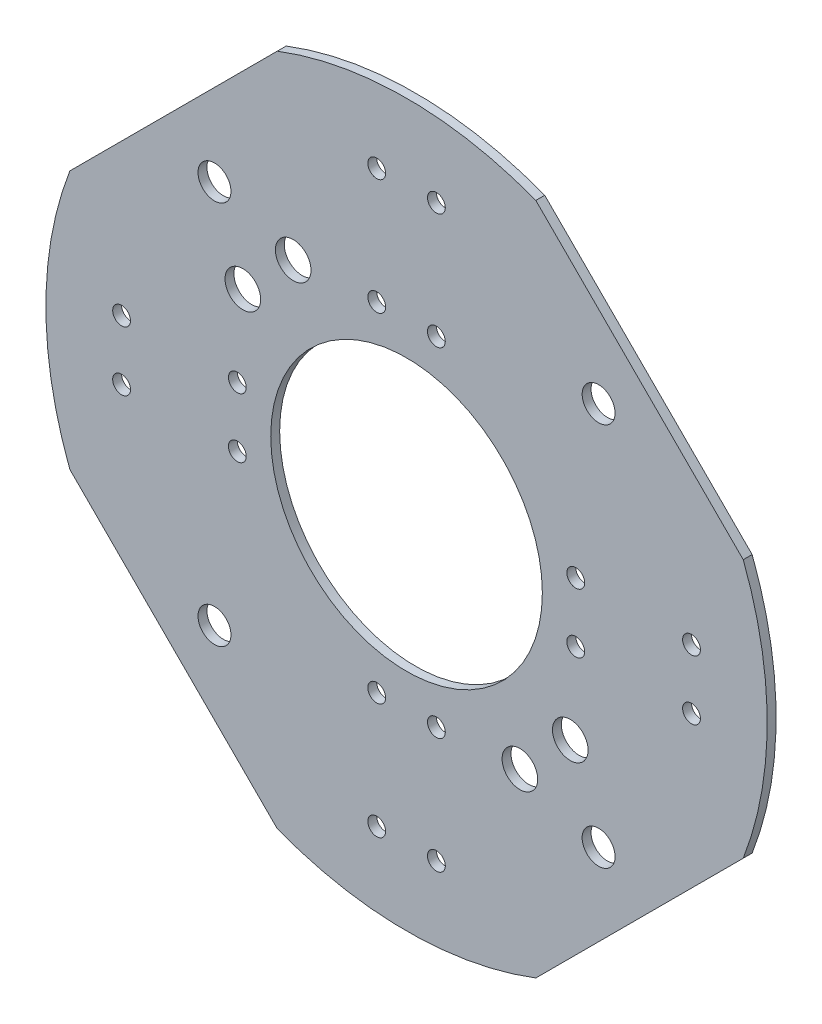
SolidWorks part; units mm, degrees
material "Epoxy, renforcé"
ref_plane "Plan de face" through (0, 0, 0) normal (0, 0, 1) x (1, 0, 0)
ref_plane "Plan de dessus" through (0, 0, 0) normal (0, 1, 0) x (1, 0, 0)
ref_plane "Plan de droite" through (0, 0, 0) normal (1, 0, 0) x (0, 0, -1)
sketch "Esquisse1" plane through (0, 0, 0) normal (0, 0, 1) x (1, 0, 0)
  line L0 (0, 0) -> (26.163, 26.163) construction
  line L1 (37.8088, 14.5171) -> (14.5171, 37.8088)
  line L2 (37.8088, -14.5171) -> (14.5171, -37.8088)
  line L3 (-14.5171, -37.8088) -> (-37.8088, -14.5171)
  line L4 (-14.5171, 37.8088) -> (-37.8088, 14.5171)
  line L5 (0, 0) -> (0, 46.5067) construction
  line L6 (0, 0) -> (-26.163, 26.163) construction
  line L7 (0, 0) -> (36.4531, 0) construction
  line L8 (19, -3.35) -> (32, -3.35) construction
  line L9 (3.35, 32) -> (3.35, 19) construction
  line L10 (32, 3.35) -> (32, -3.35) construction
  line L11 (-3.35, 32) -> (3.35, 32) construction
  circle A0 centre (0, 0) radius 15.25
  arc A1 (-37.8088, 14.5171) -> (-37.8088, -14.5171) centre (0, 0) ccw
  arc A2 (14.5171, 37.8088) -> (-14.5171, 37.8088) centre (0, 0) ccw
  arc A3 (37.8088, -14.5171) -> (37.8088, 14.5171) centre (0, 0) ccw
  arc A4 (-14.5171, -37.8088) -> (14.5171, -37.8088) centre (0, 0) ccw
  circle A5 centre (0, 0) radius 30.5 construction
  circle A6 centre (21.5668, 21.5668) radius 1.85
  circle A7 centre (-21.5668, -21.5668) radius 1.85
  circle A8 centre (-21.5668, 21.5668) radius 1.85
  circle A9 centre (21.5668, -21.5668) radius 1.85
  circle A10 centre (-12.7279, 18.3848) radius 2
  circle A11 centre (-18.3848, 12.7279) radius 2
  circle A12 centre (12.7279, -18.3848) radius 2
  circle A13 centre (18.3848, -12.7279) radius 2
  circle A14 centre (19, -3.35) radius 1
  circle A15 centre (32, -3.35) radius 1
  circle A16 centre (32, 3.35) radius 1
  circle A17 centre (19, 3.35) radius 1
  circle A18 centre (-19, -3.35) radius 1
  circle A19 centre (-32, -3.35) radius 1
  circle A20 centre (-32, 3.35) radius 1
  circle A21 centre (-19, 3.35) radius 1
  circle A22 centre (0, 0) radius 19.2931 construction
  circle A23 centre (3.35, 19) radius 1
  circle A24 centre (3.35, 32) radius 1
  circle A25 centre (-3.35, 32) radius 1
  circle A26 centre (-3.35, 19) radius 1
  circle A27 centre (3.35, -19) radius 1
  circle A28 centre (3.35, -32) radius 1
  circle A29 centre (-3.35, -32) radius 1
  circle A30 centre (-3.35, -19) radius 1
  dimension "D1" = 81
  dimension "D3" = 30.5
  dimension "D4" = 61
  dimension "D5" = 3.7
  dimension "D8" = 4
  dimension "D11" = 2
  dimension "D2" = 74
  dimension "D6" = 44
  dimension "D7" = 8
  dimension "D9" = 38
  dimension "D10" = 6.7
  dimension "D12" = 13
extrude "Boss.-Extru.1" add sketch "Esquisse1" along normal blind 1
ref_axis "Axe1" through (0, 0, 0) along (0, 0, 1)
